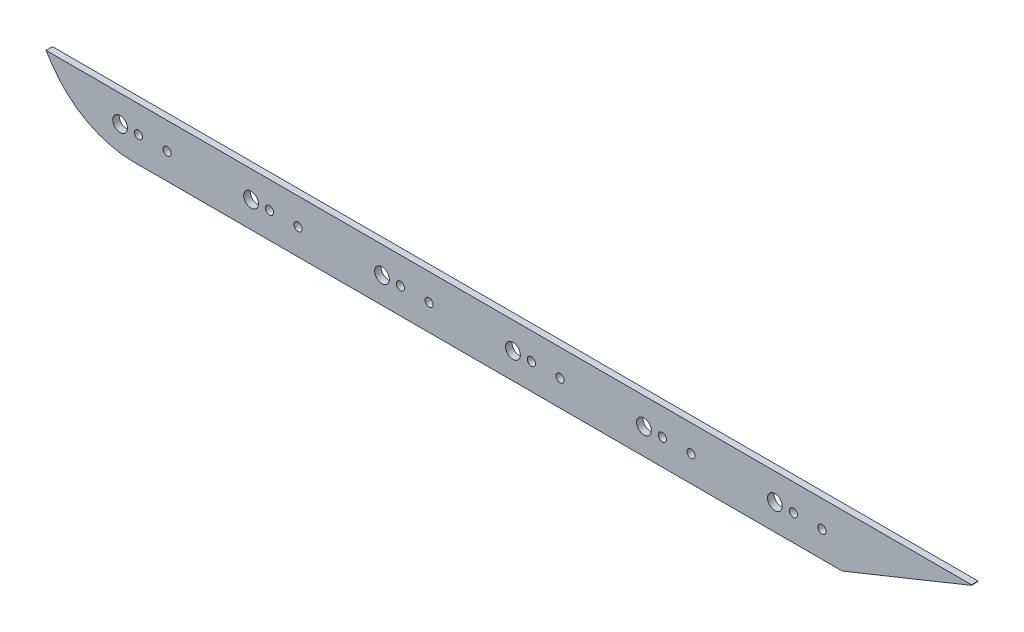
SolidWorks part; units mm, degrees
material "5052-H34"
ref_plane "Front Plane" through (0, 0, 0) normal (0, 0, 1) x (1, 0, 0)
ref_plane "Top Plane" through (0, 0, 0) normal (0, 1, 0) x (1, 0, 0)
ref_plane "Right Plane" through (0, 0, 0) normal (1, 0, 0) x (0, 0, -1)
sketch "Sketch1" plane through (0, 0, 0) normal (0, 0, 1) x (1, 0, 0)
  line L3 (428.1206, 28.9396) -> (0.5404, 28.9396)
  line L6 (-98.8794, 3.851) -> (-31.8794, -96.649)
  line L7 (428.1206, 28.9396) -> (403.1206, -71.149)
  line L9 (403.1206, -71.149) -> (366, -96.649)
  line L10 (-31.8794, -96.649) -> (366, -96.649)
  line L11 (0.5404, 28.9396) -> (-115.6052, 28.9396)
  line L12 (-98.8794, 3.851) -> (-115.6052, 28.9396)
  line L13 (-49.0861, -70.839) -> (403.198, -70.839)
  circle A0 centre (-12.8794, -83.899) radius 3.6
  circle A1 centre (51.1206, -83.899) radius 3.6
  circle A2 centre (115.1206, -83.899) radius 3.6
  circle A3 centre (179.1206, -83.899) radius 3.6
  circle A4 centre (243.1206, -83.899) radius 3.6
  circle A5 centre (307.1206, -83.899) radius 3.6
  point P0 (-48.8794, -71.149)
  point P2 (-31.8794, -96.649)
  point P8 (48, -83.899)
  point P9 (403.1206, -71.149)
  point P23 (-49.0861, -70.839)
  point P26 (403.198, -70.839)
  dimension "D2" = 64
  dimension "D4" = 64
  dimension "D1" = 25.5
  dimension "D3" = 75
  dimension "D5" = 25
  dimension "D6" = 96
  dimension "D7" = 527
  dimension "D8" = 180
  dimension "D9" = 64
  dimension "D10" = 64
  dimension "D11" = 64
  dimension "D12" = 123.69
  dimension "D13" = 12.75
  dimension "D14" = 25.81
  dimension "D15" = 25.81
extrude "Boss-Extrude1" add sketch "Sketch1" along normal blind 3.175 contours L3 L11 L12 L6 L10 L9 L7
extrude "Cut-Extrude1" cut sketch "Sketch1<4>" along normal through all contours A0 | A1 | A2 | A3 | A4 | A5 region at (-12.8794, -83.899, 0)
sketch "Sketch1<4>" plane through (0, 0, 0) normal (0, 0, 1) x (1, 0, 0) same geometry as "Sketch1"
sketch "Sketch2" plane through (0, 0, 0) normal (0, 0, -1) x (-1, 0, 0)
  circle A0 centre (-275.1206, -83.899) radius 6.5
  circle A2 centre (-233.5603, -132.5687) radius 6.5
  circle A3 centre (-192, -83.899) radius 6.5
  circle A4 centre (-128, -83.899) radius 6.5
  circle A5 centre (-64, -83.899) radius 6.5
  circle A6 centre (0, -83.899) radius 6.5
  dimension "D2" = 0
  dimension "D3" = 64
  dimension "D4" = 64
  dimension "D5" = 64
  dimension "D6" = 64
  dimension "D7" = 64
  dimension "D1" = 32
sketch "Sketch5" plane through (0, 0, 0) normal (0, 0, -1) x (-1, 0, 0)
  line L0 (48.8794, -71.149) -> (-14.2353, -96.649)
  line L1 (31.8794, -96.649) -> (-366, -96.649) construction
  line L2 (-14.2353, -96.649) -> (31.8794, -96.649)
  line L3 (31.8794, -96.649) -> (48.8794, -71.149)
  line L6 (-366, -96.649) -> (-403.1206, -71.149)
  line L7 (-403.1206, -71.149) -> (-352, -71.149)
  line L9 (-352, -71.149) -> (-326.5, -96.649)
  line L11 (-366, -96.649) -> (-326.5, -96.649)
  dimension "D1" = 22
  dimension "D2" = 45
extrude "Cut-Extrude2" [suppressed] cut sketch "Sketch5" against normal up to next
sketch "Sketch6" plane through (0, 0, 3.175) normal (0, 0, 1) x (1, 0, 0)
  line L0 (-48.8794, -71.149) -> (14.2353, -96.649)
  line L1 (-31.8794, -96.649) -> (366, -96.649) construction
  line L2 (14.2353, -96.649) -> (-31.8794, -96.649)
  line L3 (-31.8794, -96.649) -> (-48.8794, -71.149)
  dimension "D1" = 158
fillet "Fillet1" radius 48 1 edges at (-31.8794, -96.649, 1.5875)
sketch "Sketch7" plane through (0, 0, 3.175) normal (0, 0, 1) x (1, 0, 0)
  line L0 (403.1206, -71.149) -> (340.0059, -96.649)
  line L1 (-31.8794, -96.649) -> (366, -96.649) construction
  line L2 (340.0059, -96.649) -> (366, -96.649)
  line L3 (366, -96.649) -> (403.1206, -71.149)
  dimension "D1" = 22
extrude "Cut-Extrude3" cut sketch "Sketch7" against normal blind 10
sketch "Sketch9" plane through (0, 0, 0) normal (0, 0, -1) x (-1, 0, 0)
  line L0 (-403.1206, -71.149) -> (48.8794, -71.149)
  line L1 (48.8794, -71.149) -> (48.8794, -114.9143)
  line L2 (48.8794, -114.9143) -> (-403.1206, -114.9143)
  line L3 (-403.1206, -114.9143) -> (-403.1206, -71.149)
extrude "Cut-Extrude4" [suppressed] cut sketch "Sketch9" against normal blind 10
sketch "Sketch10" plane through (0, 0, 3.175) normal (0, 0, 1) x (1, 0, 0)
  line L0 (-49.0861, -70.839) -> (403.198, -70.839) construction
  line L1 (-49.0861, -70.839) -> (403.198, -70.839)
  line L2 (-49.0861, -70.839) -> (-115.6052, 28.9396)
  line L3 (-115.6052, 28.9396) -> (428.1206, 28.9396)
  line L4 (428.1206, 28.9396) -> (403.198, -70.839)
extrude "Cut-Extrude5" cut sketch "Sketch10" against normal blind 10
sketch "Sketch11" plane through (0, 0, 3.175) normal (0, 0, 1) x (1, 0, 0)
  line L0 (-12.8794, -83.899) -> (1.9194, -83.899) construction
  circle A0 centre (-3.8794, -83.899) radius 2
  circle A1 centre (10.1206, -83.899) radius 2
  circle A4 centre (60.1206, -83.899) radius 2
  circle A5 centre (74.1206, -83.899) radius 2
  circle A6 centre (124.1206, -83.899) radius 2
  circle A7 centre (138.1206, -83.899) radius 2
  circle A8 centre (188.1206, -83.899) radius 2
  circle A9 centre (202.1206, -83.899) radius 2
  circle A10 centre (252.1206, -83.899) radius 2
  circle A11 centre (266.1206, -83.899) radius 2
  circle A12 centre (316.1206, -83.899) radius 2
  circle A13 centre (330.1206, -83.899) radius 2
  dimension "D3" = 4
  dimension "D1" = 9
  dimension "D2" = 14
  dimension "D4" = 9
  dimension "D5" = 14
  dimension "D6" = 9
  dimension "D7" = 14
  dimension "D8" = 9
  dimension "D9" = 14
  dimension "D10" = 9
  dimension "D11" = 14
  dimension "D12" = 9
  dimension "D13" = 14
extrude "Cut-Extrude6" cut sketch "Sketch11" against normal blind 10
